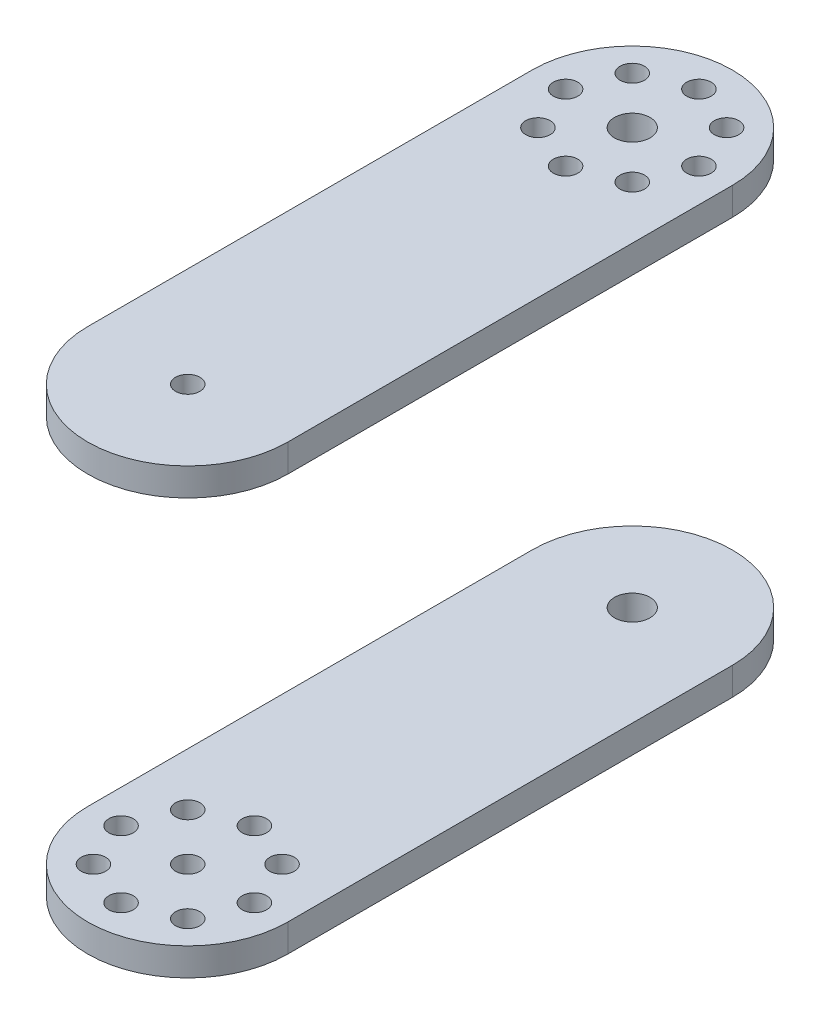
SolidWorks part; units mm, degrees
material "ABS"
ref_plane "正面" through (0, 0, 0) normal (0, 0, 1) x (1, 0, 0)
ref_plane "平面" through (0, 0, 0) normal (0, 1, 0) x (1, 0, 0)
ref_plane "右側面" through (0, 0, 0) normal (1, 0, 0) x (0, 0, -1)
sketch "ｽｹｯﾁ1" plane through (0, 0, 0) normal (0, 1, 0) x (1, 0, 0)
  line L0 (-9, 40) -> (-9, 0)
  line L2 (-10.5, 10.5) -> (-10.5, -10.5) construction
  line L8 (9, 0) -> (9, 40)
  arc A4 (9, 40) -> (-9, 40) centre (0, 40) ccw
  circle A5 centre (0, 40) radius 6 construction
  circle A6 centre (0, 46) radius 1.1
  circle A7 centre (4.2426, 44.2426) radius 1.1
  circle A8 centre (6, 40) radius 1.1
  circle A9 centre (4.2426, 35.7574) radius 1.1
  circle A10 centre (0, 34) radius 1.1
  circle A11 centre (-4.2426, 35.7574) radius 1.1
  circle A12 centre (-6, 40) radius 1.1
  circle A13 centre (-4.2426, 44.2426) radius 1.1
  circle A14 centre (0, 40) radius 1.6
  circle A15 centre (0, 0) radius 1.1
  arc A16 (-9, 0) -> (9, 0) centre (0, 0) ccw
  point P4 (0, 40)
  point P5 (-14.2989, 0)
  point P6 (20.665, 0)
  point P8 (13, 40)
  point P9 (10.4913, 11.4215)
  point P35 (0, 40)
  dimension "D2" = 9
  dimension "D3" = 2.2
  dimension "D4" = 40
  dimension "D10" = 12
  dimension "D11" = 2.2
  dimension "D13" = 3.2
  dimension "D12" = 8
extrude "ﾎﾞｽ - 押し出し1" add sketch "ｽｹｯﾁ1" along normal blind 2.5
ref_plane "平面1" through (0, -34.9, 0) normal (0, 1, 0) x (1, 0, 0)
sketch "ｽｹｯﾁ2" plane through (0, -34.9, 0) normal (0, 1, 0) x (1, 0, 0)
  line L3 (9, 0) -> (9, 40)
  line L5 (-9, 40) -> (-9, 0)
  line L6 (9, 0) -> (9, 40)
  line L8 (-9, 40) -> (-9, 0)
  circle A0 centre (0, 40) radius 1.6
  arc A1 (9, 40) -> (-9, 40) centre (0, 40) ccw
  arc A2 (9, 40) -> (-9, 40) centre (0, 40) ccw
  circle A11 centre (0, 0) radius 1.1 construction
  circle A12 centre (0, 0) radius 1.1
  arc A13 (-9, 0) -> (9, 0) centre (0, 0) ccw
  arc A14 (-9, 0) -> (9, 0) centre (0, 0) ccw
  circle A15 centre (0, 0) radius 6 construction
  circle A16 centre (0, 6) radius 1.1
  circle A17 centre (4.2426, 4.2426) radius 1.1
  circle A18 centre (6, 0) radius 1.1
  circle A19 centre (4.2426, -4.2426) radius 1.1
  circle A20 centre (0, -6) radius 1.1
  circle A21 centre (-4.2426, -4.2426) radius 1.1
  circle A22 centre (-6, 0) radius 1.1
  circle A23 centre (-4.2426, 4.2426) radius 1.1
  point P12 (4.2884, 4.2237)
  point P13 (4.6598, 0)
  point P14 (0, 0)
  point P30 (0, 0)
  dimension "D2" = 3.2
  dimension "D3" = 12
  dimension "D4" = 2.2
  dimension "D1" = 0
extrude "ﾎﾞｽ - 押し出し2" add sketch "ｽｹｯﾁ2" against normal blind 2.5 separate body
